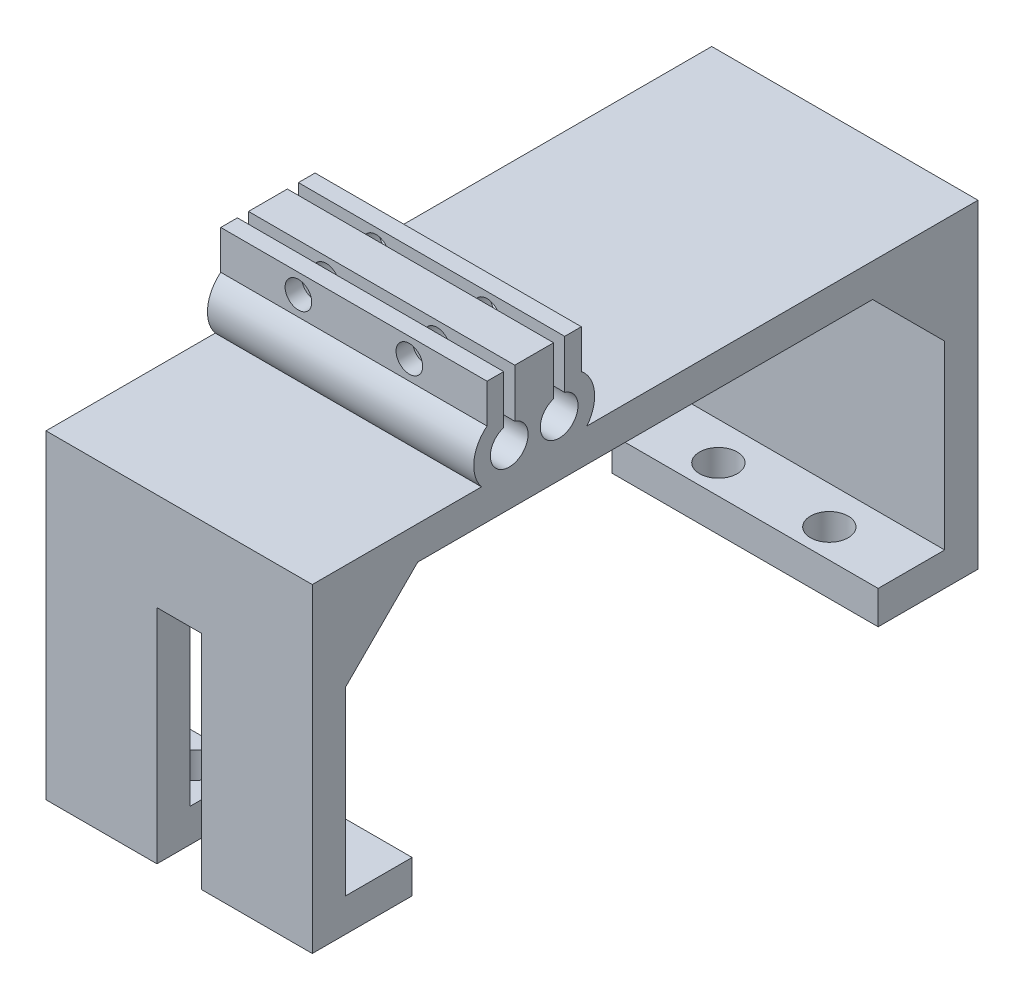
SolidWorks part; units mm, degrees
ref_plane "Front Plane" through (0, 0, 0) normal (0, 0, 1) x (1, 0, 0)
ref_plane "Top Plane" through (0, 0, 0) normal (0, 1, 0) x (1, 0, 0)
ref_plane "Right Plane" through (0, 0, 0) normal (1, 0, 0) x (0, 0, -1)
sketch "Sketch1" plane through (0, 0, 0) normal (0, 1, 0) x (1, 0, 0)
  line L1 (-12, -30) -> (12, -30)
  line L2 (-12, -30) -> (-12, 30)
  line L3 (-12, 30) -> (12, 30)
  line L4 (12, -30) -> (12, 30)
  line L5 (-12, -30) -> (12, 30) construction
  line L6 (-12, 30) -> (12, -30) construction
  point P0 (0, 0)
  dimension "D1" = 24
  dimension "D2" = 60
extrude "Boss-Extrude1" add sketch "Sketch1" along normal blind 36.8
sketch "Sketch2" plane through (12, 0, 0) normal (1, 0, 0) x (0, 0, -1)
  line L0 (-10, 36.8) -> (-10, 0) construction
  line L1 (-30, 36.8) -> (30, 36.8) construction
  line L2 (-12.25, 30.8) -> (-7.75, 30.8) construction
  line L3 (-12.75, 36.8) -> (-12.75, 32.4248)
  line L4 (-12.75, 36.8) -> (-11.75, 36.8)
  line L5 (-11.75, 36.8) -> (-11.75, 32.4248)
  line L6 (-8.25, 32.4248) -> (-8.25, 36.8)
  line L7 (-8.25, 36.8) -> (-7.25, 36.8)
  line L8 (-7.25, 36.8) -> (-7.25, 32.4248)
  line L9 (-12.25, 36.8) -> (-12.25, 30.8) construction
  line L10 (-7.75, 36.8) -> (-7.75, 30.8) construction
  line L11 (-30, 0) -> (30, 0) construction
  circle A0 centre (-12.25, 30.8) radius 1.7 construction
  circle A1 centre (-7.75, 30.8) radius 1.7 construction
  arc A2 (-12.75, 32.4248) -> (-11.75, 32.4248) centre (-12.25, 30.8) ccw
  arc A3 (-8.25, 32.4248) -> (-7.25, 32.4248) centre (-7.75, 30.8) ccw
  point P8 (-10, 30.8)
  dimension "D1" = 3.4
  dimension "D2" = 3.4
  dimension "D3" = 4.5
  dimension "D4" = 6
  dimension "D5" = 1
  dimension "D6" = 1
  dimension "D7" = 10
extrude "Cut-Extrude1" cut sketch "Sketch2" against normal through all
sketch "Sketch3" plane through (12, 0, 0) normal (1, 0, 0) x (0, 0, -1)
  line L1 (-14.25, 36.8) -> (-14.25, 33.298)
  line L2 (-30, 36.8) -> (-12.75, 36.8) construction
  line L3 (-10, 36.8) -> (-10, 0) construction
  line L6 (-12.75, 36.8) -> (-12.75, 32.4248) construction
  line L7 (-14.748, 28.8) -> (-30, 28.8)
  line L8 (-30, 36.8) -> (-30, 0) construction
  line L9 (-30, 28.8) -> (-30, 36.8)
  line L10 (-30, 36.8) -> (-14.25, 36.8)
  line L11 (30, 28.8) -> (30, 36.8)
  line L12 (-5.252, 28.8) -> (30, 28.8)
  line L13 (-5.75, 36.8) -> (-5.75, 33.298)
  line L14 (30, 36.8) -> (-5.75, 36.8)
  line L15 (-30, 0) -> (30, 0) construction
  line L16 (-11.75, 36.8) -> (-8.25, 36.8) construction
  line L17 (30, 36.8) -> (30, 0) construction
  arc A0 (-14.25, 33.298) -> (-14.748, 28.8) centre (-12.25, 30.8) ccw
  arc A1 (-12.75, 32.4248) -> (-11.75, 32.4248) centre (-12.25, 30.8) ccw construction
  arc A2 (-5.75, 33.298) -> (-5.252, 28.8) centre (-7.75, 30.8) cw
  dimension "D2" = 1.5
  dimension "D1" = 1.5
  dimension "D3" = 8
extrude "Cut-Extrude2" cut sketch "Sketch3" against normal through all
sketch "Sketch4" plane through (0, 0, 5.75) normal (0, 0, -1) x (-1, 0, 0)
  line L0 (0, 20.0902) -> (0, 0) construction
  line L1 (-5, 35.049) -> (5, 35.049) construction
  line L2 (-12, 35.049) -> (12, 35.049) construction
  line L3 (-12, 36.8) -> (-12, 33.298) construction
  line L4 (12, 36.8) -> (12, 33.298) construction
  circle A0 centre (-5, 35.049) radius 1.2
  circle A1 centre (5, 35.049) radius 1.2
  point P6 (0, 35.049)
  dimension "D2" = 2.4
  dimension "D1" = 10
extrude "Cut-Extrude3" cut sketch "Sketch4" against normal through all
sketch "Sketch5" plane through (12, 0, 0) normal (1, 0, 0) x (0, 0, -1)
  line L0 (-27, 25.8) -> (-27, 0)
  line L1 (-27, 25.8) -> (27, 25.8)
  line L2 (-27, 0) -> (27, 0)
  line L3 (27, 25.8) -> (27, 0)
  line L4 (-27, 25.8) -> (27, 0) construction
  line L5 (-27, 0) -> (27, 25.8) construction
  line L6 (-5.252, 28.8) -> (30, 28.8) construction
  line L7 (-30, 28.8) -> (-30, 0) construction
  point P0 (0, 0)
  point P1 (0, 12.9)
  dimension "D1" = 3
  dimension "D2" = 3
extrude "Cut-Extrude4" cut sketch "Sketch5" against normal through all
sketch "Sketch6" plane through (0, 0, -30) normal (0, 0, -1) x (-1, 0, 0)
  line L0 (12, 28.8) -> (12, 0) construction
  line L1 (-12, 0) -> (12, 0)
  line L2 (-12, 0) -> (-12, 3)
  line L3 (-12, 3) -> (12, 3)
  line L4 (12, 0) -> (12, 3)
  dimension "D1" = 3
extrude "Boss-Extrude2" add sketch "Sketch6" against normal blind 9
sketch "Sketch7" plane through (0, 0, 30) normal (0, 0, 1) x (1, 0, 0)
  line L0 (12, 28.8) -> (12, 0) construction
  line L1 (-12, 0) -> (12, 0)
  line L2 (-12, 0) -> (-12, 3)
  line L3 (-12, 3) -> (12, 3)
  line L4 (12, 0) -> (12, 3)
  dimension "D1" = 3
extrude "Boss-Extrude3" add sketch "Sketch7" against normal blind 9
sketch "Sketch8" plane through (0, 3, 0) normal (0, 1, 0) x (1, 0, 0)
  line L1 (-5, -23.6) -> (5, -23.6) construction
  line L2 (-5, -23.6) -> (-5, 23.6) construction
  line L3 (-5, 23.6) -> (5, 23.6) construction
  line L4 (5, -23.6) -> (5, 23.6) construction
  line L5 (-5, -23.6) -> (5, 23.6) construction
  line L6 (-5, 23.6) -> (5, -23.6) construction
  circle A0 centre (-5, 23.6) radius 1.7
  circle A1 centre (5, 23.6) radius 1.7
  circle A2 centre (-5, -23.6) radius 1.7
  circle A3 centre (5, -23.6) radius 1.7
  point P0 (0, 0)
  dimension "D3" = 3.4
  dimension "D1" = 10
  dimension "D2" = 47.2
extrude "Cut-Extrude5" cut sketch "Sketch8" against normal blind 6
sketch "Sketch9" plane through (0, 0, 30) normal (0, 0, 1) x (1, 0, 0)
  line L0 (-2, 20) -> (-2, 0)
  line L1 (-2, 20) -> (2, 20)
  line L2 (-2, 0) -> (2, 0)
  line L3 (2, 20) -> (2, 0)
  line L4 (-2, 20) -> (2, 0) construction
  line L5 (-2, 0) -> (2, 20) construction
  point P0 (0, 0)
  point P1 (0, 10)
  dimension "D1" = 20
  dimension "D2" = 4
extrude "Cut-Extrude6" cut sketch "Sketch9" against normal blind 17
chamfer "Chamfer1" distance 6.5 angle 45 2 edges at (0, 25.8, -27) (0, 25.8, 27)
